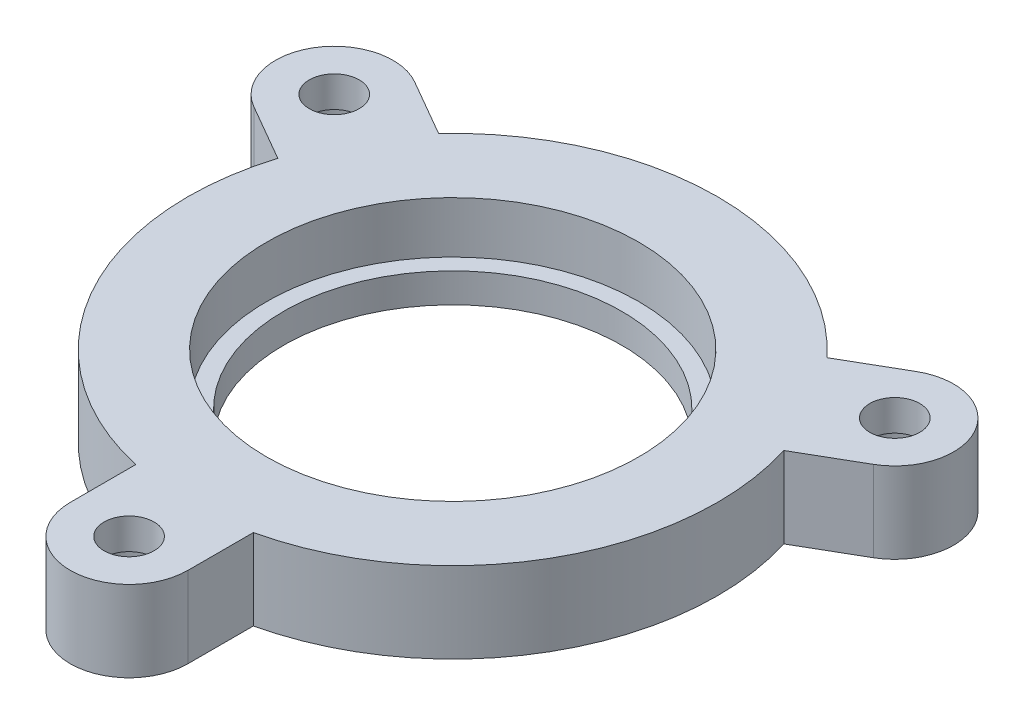
SolidWorks part; units mm, degrees
ref_plane "Front Plane" through (0, 0, 0) normal (0, 0, 1) x (1, 0, 0)
ref_plane "Top Plane" through (0, 0, 0) normal (0, 1, 0) x (1, 0, 0)
ref_plane "Right Plane" through (0, 0, 0) normal (1, 0, 0) x (0, 0, -1)
sketch "Sketch1" plane through (0, 0, 0) normal (0, 1, 0) x (1, 0, 0)
  line L0 (4, -22) -> (4, -17.5499)
  line L1 (-4, -22) -> (-4, -17.5499)
  line L2 (-21.0526, 7.5359) -> (-17.1987, 5.3109)
  line L3 (-17.0526, 14.4641) -> (-13.1987, 12.2391)
  line L4 (17.0526, 14.4641) -> (13.1987, 12.2391)
  line L5 (21.0526, 7.5359) -> (17.1987, 5.3109)
  circle A0 centre (0, 0) radius 18
  circle A1 centre (0, 0) radius 11.5
  circle A2 centre (0, -22) radius 4
  circle A3 centre (0, -22) radius 2.1 construction
  circle A4 centre (0, 0) radius 12.65
  circle A5 centre (-19.0526, 11) radius 2.1 construction
  circle A6 centre (-19.0526, 11) radius 4
  circle A7 centre (19.0526, 11) radius 2.1 construction
  circle A8 centre (19.0526, 11) radius 4
  point P28 (0, 0)
  dimension "D2" = 36
  dimension "D3" = 23
  dimension "D4" = 4.2
  dimension "D5" = 8
  dimension "D6" = 25.3
  dimension "D1" = 22
  dimension "D7" = 3
extrude "Boss-Extrude1" add sketch "Sketch1" along normal blind 5.5 contours A2 L0 A0 | A2 A0 L1 | A2 A3 | A6 A5 | A6 A0 L3 | A6 L2 A0 | A8 A7 | A8 A0 L5 | A8 L4 A0 | A1 | A0 region at (3.0911, 0, 18.7412) region at (0, 0, 22) region at (-3.0911, 0, 18.7412) region at (17.7759, 0, -6.6936) region at (-17.7759, 0, -6.6936) region at (19.0526, 0, -11) region at (14.6848, 0, -12.0476) region at (-19.0526, 0, -11) region at (-14.6848, 0, -12.0476) region at (0, 0, 0)
extrude "Cut-Extrude1" cut sketch "Sketch1<3>" against normal blind 3.5 from surface contours A4 starting at face at (0, 5.5, 0)
sketch "Sketch1<3>" plane through (0, 0, 0) normal (0, 1, 0) x (1, 0, 0) same geometry as "Sketch1"
hole_wizard "CBORE for M3 Hex Socket Head Cap Screw1" positions "Sketch2" profile "Sketch4" counterbore size "M3" standard "ISO"
sketch "Sketch2" plane through (0, 0, 0) normal (0, 1, 0) x (1, 0, 0)
  point P0 (-19.0526, 11)
  point P3 (19.0526, 11)
  point P6 (0, -22)
sketch "Sketch4" plane through (-19.0526, 0, -11) normal (1, 0, 0) x (0, 0, -1)
  line L0 (0, 0) -> (0, 46.0215)
  line L1 (0, 46.0215) -> (1.7, 45)
  line L2 (1.7, 45) -> (1.7, 3.4)
  line L3 (1.7, 3.4) -> (3.25, 3.4)
  line L4 (3.25, 3.4) -> (3.25, 0)
  line L5 (3.25, 0) -> (0, 0)
  line L10 (0, 46.0215) -> (-1.7, 45) construction
  line L11 (0, -6.35) -> (0, 107.95) construction
  dimension "Hole Dia." = 3.4
  dimension "Hole Depth" = 45
  dimension "C'Bore Dia." = 6.5
  dimension "C'Bore Depth" = 3.4
  dimension "Drill Angle" = 118
